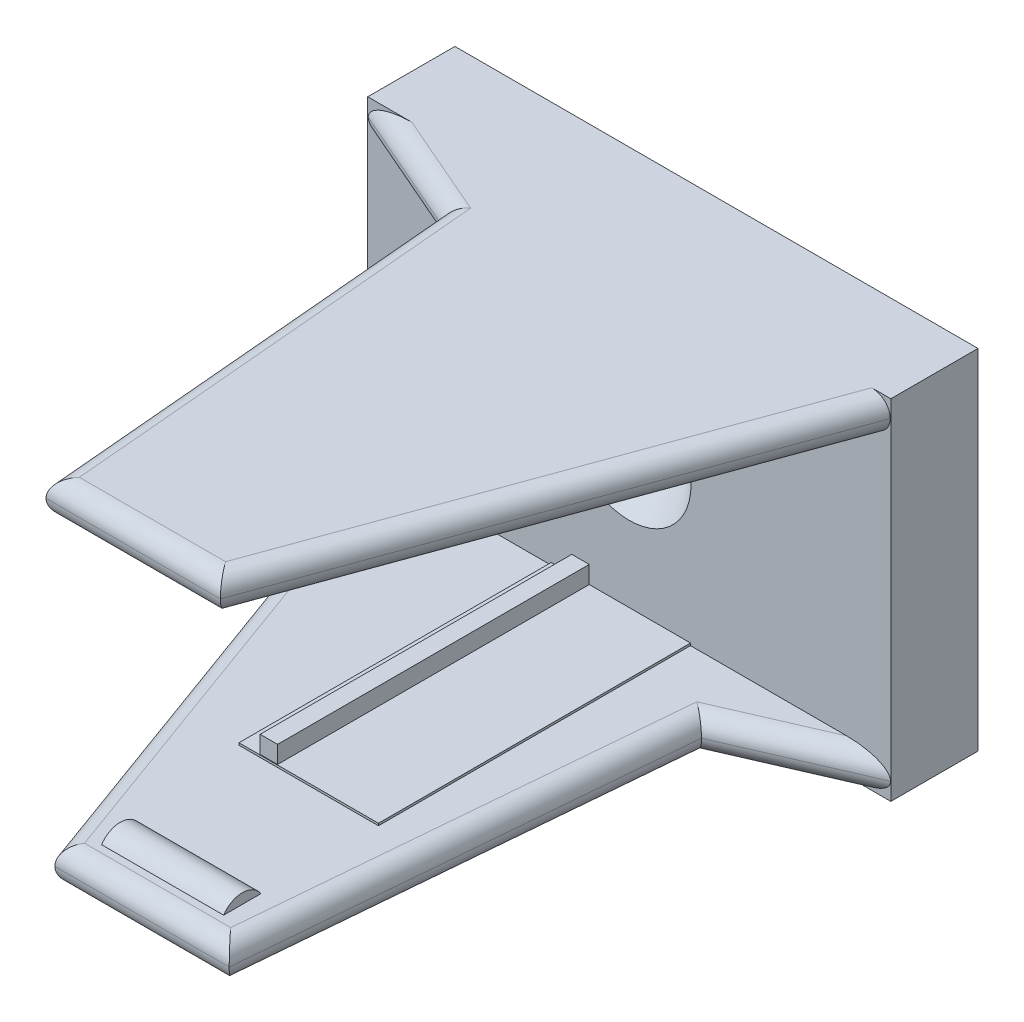
SolidWorks part; units mm, degrees
ref_plane "Plan de face" through (0, 0, 0) normal (0, 0, 1) x (1, 0, 0)
ref_plane "Plan de dessus" through (0, 0, 0) normal (0, 1, 0) x (1, 0, 0)
ref_plane "Plan de droite" through (0, 0, 0) normal (1, 0, 0) x (0, 0, -1)
sketch "Esquisse1" plane through (0, 0, 0) normal (0, 0, 1) x (1, 0, 0)
  line L1 (-27.0629, 34) -> (20, 34)
  line L2 (-27.0629, 34) -> (-27.0629, -17.1626)
  line L3 (-27.0629, -17.1626) -> (20, -17.1626)
  line L4 (20, 34) -> (20, -17.1626)
  line L5 (30, 0) -> (0, 0)
  line L6 (30, 0) -> (30, 20)
  line L7 (30, 20) -> (0, 20)
  line L8 (0, 0) -> (0, 20)
extrude "Boss.-Extru.3" add sketch "Esquisse1" along normal blind 5 contours L6 L7 L4 L5 | L8 L5 L4 L7 region at (25, 10, 0) region at (10, 10, 0)
sketch "Esquisse14" plane through (0, 20, 0) normal (0, 1, 0) x (1, 0, 0)
  line L0 (29.9775, -4.9784) -> (19.7169, -33.1692)
  line L1 (19.7169, -33.1692) -> (9.7169, -33.1692)
  line L2 (9.7169, -33.1692) -> (7.538, -8.2643)
  line L3 (7.538, -8.2643) -> (-0.0225, -4.9784)
  line L4 (-0.0225, -4.9784) -> (29.9775, -4.9784)
extrude "Boss.-Extru.5" add sketch "Esquisse14" against normal blind 2
sketch "Esquisse15" plane through (0, 18, 0) normal (0, -1, 0) x (-1, 0, 0)
  line L1 (-10.8236, -22.9134) -> (-18.8236, -22.9134)
  line L2 (-10.8236, -22.9134) -> (-10.8236, -5)
  line L3 (-10.8236, -5) -> (-18.8236, -5)
  line L4 (-18.8236, -22.9134) -> (-18.8236, -5)
  line L5 (-29.9697, -5) -> (-0.0272, -5) construction
extrude "Boss.-Extru.6" add sketch "Esquisse15" along normal blind 0.1 contours L1 L4 L3 L2
sketch "Esquisse16" plane through (0, 17.9, 0) normal (0, -1, 0) x (1, 0, 0)
  line L0 (10.8236, 5) -> (18.8236, 5) construction
  line L1 (10.8236, 22.9134) -> (18.8236, 22.9134) construction
  line L2 (11.8236, 5) -> (12.8236, 5)
  line L3 (11.8236, 5) -> (11.8236, 22.9134)
  line L4 (11.8236, 22.9134) -> (12.8236, 22.9134)
  line L5 (12.8236, 5) -> (12.8236, 22.9134)
extrude "Boss.-Extru.7" add sketch "Esquisse16" along normal blind 1 contours L5 L4 L3 L2
sketch "Esquisse20" plane through (0, 0, 0) normal (0, -1, 0) x (-1, 0, 0)
  line L0 (0.0078, -5.0065) -> (-10.2528, -33.1973)
  line L1 (-10.2528, -33.1973) -> (-20.2528, -33.1973)
  line L2 (-20.2528, -33.1973) -> (-22.4317, -8.2924)
  line L3 (-22.4317, -8.2924) -> (-29.9922, -5.0065)
  line L4 (-29.9922, -5.0065) -> (0.0078, -5.0065)
extrude "Boss.-Extru.11" add sketch "Esquisse20" against normal blind 2 separate body
sketch "Esquisse32" plane through (0, 2, 0) normal (0, 1, 0) x (1, 0, 0)
  line L0 (18.5168, -22.903) -> (10.5168, -22.903)
  line L1 (18.5168, -22.903) -> (18.5168, -4.9895)
  line L2 (18.5168, -4.9895) -> (10.5168, -4.9895)
  line L3 (10.5168, -22.903) -> (10.5168, -4.9895)
extrude "Boss.-Extru.14" add sketch "Esquisse32" along normal blind 0.125 contours L0 L3 L2 L1
sketch "Esquisse42" plane through (18.5168, 0, 0) normal (1, 0, 0) x (0, 0, -1)
  circle A0 centre (-30.7104, 1.3) radius 1.2791
extrude "Boss.-Extru.18" add sketch "Esquisse42" against normal blind 7
sketch "Esquisse56" plane through (18.8236, 0, 0) normal (1, 0, 0) x (0, 0, -1)
  circle A0 centre (-30.4759, 18.6426) radius 1.3
extrude "Boss.-Extru.20" add sketch "Esquisse56" against normal blind 7 contours A0
fillet "Congé4" radius 1 17 edges at (-0.0078, 1, 5.0065) (5.1225, 2, 19.1019) (5.1225, 0, 19.1019) (15.2528, 0, 33.1973) (15.2528, 2, 33.1973) (21.3422, 2, 20.7448) (21.3422, 0, 20.7448) (26.2119, 2, 6.6494) (26.2119, 0, 6.6494) (3.7826, 18, 6.6322) (3.7826, 20, 6.6322) (8.6275, 18, 20.7168) (8.6275, 20, 20.7168) (14.7169, 18, 33.1692) (14.7169, 20, 33.1692) (24.8433, 18, 19.0846) (24.8433, 20, 19.0846)
sketch "Esquisse33" plane through (0, 2.125, 0) normal (0, 1, 0) x (-1, 0, 0)
  line L2 (-12.7038, 4.9625) -> (-11.7038, 4.9625)
  line L3 (-12.7038, 4.9625) -> (-12.7038, 22.8759)
  line L4 (-12.7038, 22.8759) -> (-11.7038, 22.8759)
  line L5 (-11.7038, 4.9625) -> (-11.7038, 22.8759)
extrude "Boss.-Extru.15" add sketch "Esquisse33" along normal blind 1 contours L5 L4 L3 L2
sketch "Esquisse35" plane through (0, 0, 5) normal (0, 0, 1) x (1, 0, 0)
  circle A1 centre (15, 10) radius 2.1282
extrude "Enlèv. mat.-Extru.1" cut sketch "Esquisse35" against normal blind 5 contours A1
sketch "Esquisse37" plane through (0, 0, 0) normal (0, 0, -1) x (-1, 0, 0)
  line L1 (-2, 18) -> (-28, 18)
  line L2 (-2, 18) -> (-2, 2)
  line L3 (-2, 2) -> (-28, 2)
  line L4 (-28, 18) -> (-28, 2)
extrude "Enlèv. mat.-Extru.2" cut sketch "Esquisse37" against normal blind 3 contours L1 L4 L3 L2
sketch "Esquisse38" plane through (0, 0, 3) normal (0, 0, -1) x (-1, 0, 0)
  circle A0 centre (-15, 10) radius 3.5
extrude "Boss.-Extru.17" add sketch "Esquisse38" along normal blind 3
extrude "Enlèv. mat.-Extru.3" cut sketch "Esquisse35<3>" against normal blind 5 contours A1
sketch "Esquisse35<3>" plane through (0, 0, 5) normal (0, 0, 1) x (1, 0, 0) same geometry as "Esquisse35"
hole_wizard "Fraisage pour vis à tête fraisée bombée #61" positions "Esquisse63" profile "Esquisse62" countersink size "#6" standard "Ansi Inch" end condition through all
sketch "Esquisse63" plane through (0, 0, 5) normal (0, 0, 1) x (1, 0, 0)
  point P0 (15, 10)
sketch "Esquisse62" plane through (15, 10, 5) normal (1, 0, 0) x (0, -1, 0)
  line L0 (0, 0) -> (0, 5)
  line L1 (0, 5) -> (1.8986, 5)
  line L2 (1.8986, 5) -> (1.8986, 1.892)
  line L3 (1.8986, 1.892) -> (3.5433, 0)
  line L5 (3.5433, 0) -> (0, 0)
  line L6 (-1.8986, 1.892) -> (-3.5433, 0) construction
  line L11 (0, -6.35) -> (0, 107.95) construction
  dimension "Diamètre du perçage jusqu'au prochain" = 3.7973
  dimension "Profondeur du perçage jusqu'au prochain" = 5
  dimension "Diamètre du fraisage entrant" = 7.0866
  dimension "Angle du fraisage entrant" = 82
